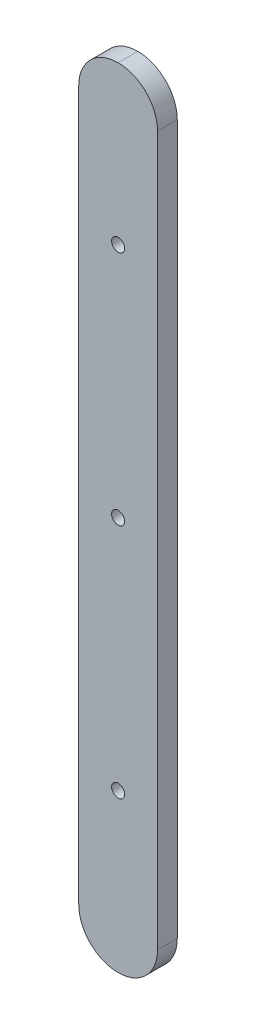
SolidWorks part; units mm, degrees
material "Acrylic (Medium-high impact)"
ref_plane "Front Plane" through (0, 0, 0) normal (0, 0, 1) x (1, 0, 0)
ref_plane "Top Plane" through (0, 0, 0) normal (0, 1, 0) x (1, 0, 0)
ref_plane "Right Plane" through (0, 0, 0) normal (1, 0, 0) x (0, 0, -1)
sketch "Sketch1" plane through (0, 0, 0) normal (0, 0, 1) x (1, 0, 0)
  line L1 (0, 0) -> (20, 0)
  line L2 (0, 0) -> (0, 200)
  line L3 (0, 200) -> (20, 200)
  line L4 (20, 0) -> (20, 200)
  circle A0 centre (10, 160) radius 1.65
  circle A1 centre (10, 100) radius 1.65
  circle A2 centre (10, 40) radius 1.65
  dimension "D3" = 3.3
  dimension "D1" = 20
  dimension "D2" = 200
  dimension "D4" = 40
  dimension "D5" = 3
extrude "Boss-Extrude1" add sketch "Sketch1" along normal blind 5
fillet "Fillet1" radius 10 4 edges at (0, 0, 2.5) (20, 0, 2.5) (20, 200, 2.5) (0, 200, 2.5)
